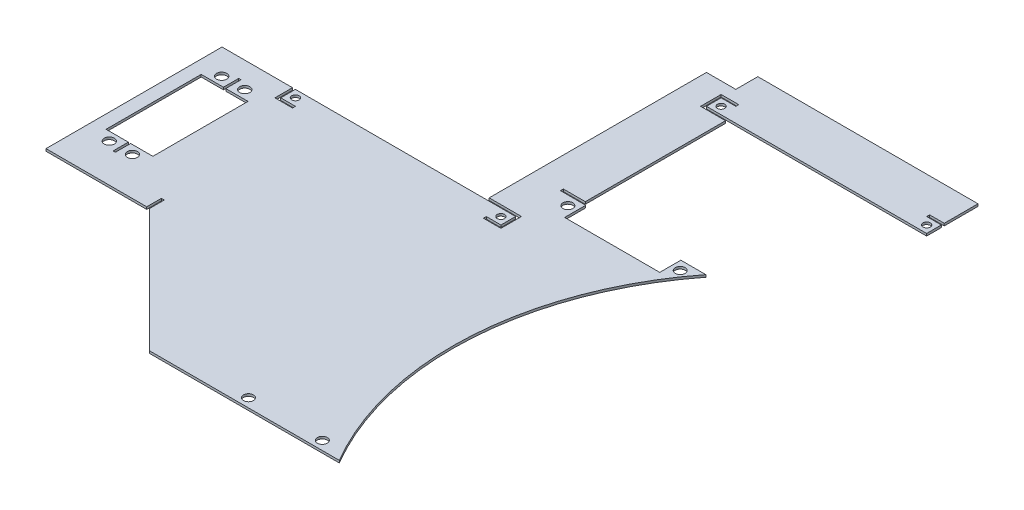
SolidWorks part; units mm, degrees
ref_plane "Front Plane" through (0, 0, 0) normal (0, 0, 1) x (1, 0, 0)
ref_plane "Top Plane" through (0, 0, 0) normal (0, 1, 0) x (1, 0, 0)
ref_plane "Right Plane" through (0, 0, 0) normal (1, 0, 0) x (0, 0, -1)
sketch "Sketch2" plane through (0, 0, 0) normal (0, 1, 0) x (1, 0, 0)
  line L1 (-127, -127) -> (127, -127)
  line L2 (-127, -127) -> (-127, 127)
  line L3 (-127, 127) -> (127, 127)
  line L4 (127, -127) -> (127, 127)
  line L5 (-127, -127) -> (127, 127) construction
  line L6 (-127, 127) -> (127, -127) construction
  point P0 (0, 0)
  dimension "D1" = 254
  dimension "D2" = 254
extrude "Boss-Extrude1" add sketch "Sketch2" along normal blind 1.0008 contours L3 L4 L1 L2
sketch "Sketch3" plane through (0, 1.0008, 0) normal (0, 1, 0) x (1, 0, 0)
  line L0 (63.5, 41.91) -> (63.5, 3.81) construction
  line L1 (127, 47.252) -> (57.15, 47.252)
  line L2 (127, 47.252) -> (127, 21.852)
  line L3 (127, 21.852) -> (57.15, 21.852)
  line L4 (57.15, 47.252) -> (57.15, 21.852)
  line L7 (64.096, 22.36) -> (70.7, 22.36) construction
  line L8 (64.096, 22.36) -> (70.7, 22.36) construction
  dimension "D1" = 6.35
  dimension "D2" = 0.508
  dimension "D3" = 25.4
extrude "Cut-Extrude1" cut sketch "Sketch3" against normal through all both and the other way through all
sketch "Sketch4" plane through (0, 1.0008, 0) normal (0, 1, 0) x (1, 0, 0)
  line L6 (127, -127) -> (127, 21.852)
  line L8 (127, 21.852) -> (57.15, 21.852)
  line L9 (127, 127) -> (-127, 127)
  line L10 (-127, 127) -> (-127, -127)
  line L11 (-127, -127) -> (127, -127)
  line L12 (127, -127) -> (127, 21.852)
  line L17 (112.9689, -127) -> (127, -127)
  line L18 (127, 21.852) -> (122.64, 21.852)
  line L19 (57.15, 21.852) -> (57.15, 47.252)
  line L22 (57.15, 47.252) -> (127, 47.252)
  line L24 (127, 47.252) -> (127, 127)
  arc A0 (127, 27.1603) -> (114.5024, -129.54) centre (227.33, -59.69) ccw construction
  arc A1 (122.64, 21.852) -> (112.9689, -127) centre (227.33, -59.69) ccw
  dimension "D1" = 0
extrude "Cut-Extrude2" cut sketch "Sketch4" against normal through all both
sketch "Sketch5" plane through (0, 1.0008, 0) normal (0, 1, 0) x (1, 0, 0)
  line L0 (63.5, -129.54) -> (63.5, -61.2891) construction
  circle A0 centre (115.577, 17.86) radius 2.1 construction
  circle A1 centre (66.977, 17.86) radius 2.1 construction
  circle A2 centre (115.577, 17.86) radius 2.1 construction
  circle A3 centre (66.977, 17.86) radius 2.1 construction
  circle A4 centre (69.85, -123.19) radius 2.15
  circle A5 centre (101.8024, -123.19) radius 2.15
  circle A6 centre (66.977, 17.86) radius 2.15
  circle A7 centre (115.577, 17.86) radius 2.15
  dimension "D1" = 6.35
  dimension "D5" = 4.3
  dimension "D2" = 12.7
  dimension "D3" = 6.35
  dimension "D4" = 6.35
extrude "Cut-Extrude3" cut sketch "Sketch5" against normal through all both
sketch "Sketch6" plane through (0, 1.0008, 0) normal (0, 1, 0) x (1, 0, 0)
  line L12 (70.7, 22.36) -> (70.7, 12.733)
  line L13 (70.7, 12.733) -> (111.854, 12.733)
  line L14 (111.854, 12.733) -> (111.854, 22.36)
  line L15 (111.854, 22.36) -> (118.458, 22.36)
  line L16 (118.458, 22.36) -> (118.458, 23.36)
  line L17 (118.458, 23.36) -> (111.854, 23.36)
  line L18 (111.854, 23.36) -> (111.854, 32.987)
  line L19 (111.854, 32.987) -> (70.7, 32.987)
  line L20 (70.7, 32.987) -> (70.7, 23.36)
  line L21 (70.7, 23.36) -> (64.096, 23.36)
  line L22 (64.096, 23.36) -> (64.096, 22.36)
  line L23 (64.096, 22.36) -> (70.7, 22.36)
  line L24 (70.7, 22.36) -> (70.7, 12.733)
  line L25 (70.7, 12.733) -> (111.854, 12.733)
  line L26 (111.854, 12.733) -> (111.854, 22.36)
  line L27 (111.854, 22.36) -> (118.458, 22.36)
  line L28 (118.458, 22.36) -> (118.458, 23.36)
  line L29 (118.458, 23.36) -> (111.854, 23.36)
  line L30 (111.854, 23.36) -> (111.854, 32.987)
  line L31 (111.854, 32.987) -> (70.7, 32.987)
  line L32 (70.7, 32.987) -> (70.7, 23.36)
  line L33 (70.7, 23.36) -> (64.096, 23.36)
  line L34 (64.096, 23.36) -> (64.096, 22.36)
  line L35 (64.096, 22.36) -> (70.7, 22.36)
  circle A1 centre (66.977, 27.86) radius 2.1
  circle A2 centre (66.977, 27.86) radius 2.1
  circle A3 centre (66.977, 17.86) radius 2.1
  circle A4 centre (66.977, 17.86) radius 2.1
  circle A5 centre (115.577, 27.86) radius 2.1
  circle A6 centre (115.577, 27.86) radius 2.1
  circle A7 centre (115.577, 17.86) radius 2.1
  circle A8 centre (115.577, 17.86) radius 2.1
  dimension "D1" = 0
  dimension "D2" = 0
  dimension "D3" = 0
  dimension "D4" = 0
  dimension "D5" = 0
extrude "Cut-Extrude4" cut sketch "Sketch6" against normal through all both
sketch "Sketch7" plane through (0, 1.0008, 0) normal (0, 1, 0) x (1, 0, 0)
  line L1 (-35.5092, 2.4892) -> (59.7408, 2.4892)
  line L2 (-35.5092, 2.4892) -> (-35.5092, 97.7392)
  line L3 (-35.5092, 97.7392) -> (59.7408, 97.7392)
  line L4 (59.7408, 2.4892) -> (59.7408, 97.7392)
  line L5 (-35.5092, 2.4892) -> (59.7408, 97.7392) construction
  line L6 (-35.5092, 97.7392) -> (59.7408, 2.4892) construction
  circle A2 centre (101.6, 22.86) radius 4.7625 construction
  circle A3 centre (101.6, 22.86) radius 4.699 construction
  point P0 (12.1158, 50.1142)
  dimension "D1" = 95.25
  dimension "D3" = 20.3708
  dimension "D2" = 137.1092
extrude "Cut-Extrude5" cut sketch "Sketch7" against normal through all both
sketch "Sketch8" plane through (0, 1.0008, 0) normal (0, 1, 0) x (1, 0, 0)
  line L0 (127, 47.252) -> (127, 127)
  line L2 (127, 127) -> (-127, 127)
  line L3 (-127, 127) -> (-127, -127)
  line L4 (-127, -127) -> (-35.5092, -127)
  line L5 (-127, -127) -> (112.9689, -127) construction
  line L6 (-35.5092, -127) -> (-35.5092, 47.252)
  line L7 (-35.5092, 47.252) -> (127, 47.252)
  line L9 (-35.5092, 97.7392) -> (-35.5092, 2.4892) construction
  point P2 (0, 0)
extrude "Cut-Extrude6" cut sketch "Sketch8" against normal through all both
sketch "Sketch17" plane through (0, 1.0008, 0) normal (0, 1, 0) x (1, 0, 0)
  line L1 (59.7408, 2.4892) -> (47.0408, 2.4892)
  line L2 (59.7408, 2.4892) -> (59.7408, 85.0392)
  line L3 (59.7408, 97.7392) -> (47.0408, 97.7392)
  line L4 (47.0408, 2.4892) -> (47.0408, 97.7392)
  line L5 (-35.5092, 2.4892) -> (59.7408, 2.4892) construction
  line L6 (59.7408, 97.7392) -> (154.9908, 97.7392)
  line L8 (59.7408, 85.0392) -> (154.9908, 85.0392)
  line L9 (154.9908, 97.7392) -> (154.9908, 85.0392)
  dimension "D1" = 12.7
extrude "Boss-Extrude4" add sketch "Sketch17" against normal up to surface (1.0008 mm away) up to face at (62.6286, 0, 13.466)
sketch "Sketch18" plane through (0, 1.0008, 0) normal (0, 1, 0) x (1, 0, 0)
  line L0 (47.0408, 2.4892) -> (59.7408, 2.4892)
  point P3 (0, 0)
extrude "Cut-Extrude-Thin4" cut sketch "Sketch18" against normal through all both and the other way through all thin thin type one direction reverse wall 1.27
sketch "Sketch9" plane through (0, 1.0008, 0) normal (0, 1, 0) x (1, 0, 0)
  line L0 (-35.5092, -60.5651) -> (30.9257, -127)
  line L1 (-35.5092, -127) -> (-35.5092, 2.4892) construction
  line L2 (-35.5092, -127) -> (112.9689, -127) construction
  line L3 (-35.5092, -127) -> (30.9257, -127)
  line L4 (-35.5092, -127) -> (-35.5092, -60.5651)
  circle A0 centre (101.727, 22.86) radius 149.6811 construction
  circle A1 centre (101.727, 22.86) radius 156.0311 construction
  dimension "D1" = 6.35
  dimension "D2" = 45
extrude "Cut-Extrude7" cut sketch "Sketch9" against normal through all both
sketch "Sketch10" plane through (0, 1.0008, 0) normal (0, 1, 0) x (1, 0, 0)
  line L37 (59.7408, 21.852) -> (59.7408, 85.0392) construction
  line L38 (59.7408, 83.7692) -> (69.2658, 83.7692)
  line L39 (59.7408, 83.7692) -> (59.7408, 23.122)
  line L40 (59.7408, 23.122) -> (69.2658, 23.122)
  line L41 (69.2658, 83.7692) -> (69.2658, 23.122)
  line L42 (70.7, 21.852) -> (59.7408, 21.852) construction
  line L43 (59.7408, 85.0392) -> (154.9908, 85.0392) construction
  line L44 (154.9908, 97.7392) -> (47.0408, 97.7392) construction
  line L45 (59.7408, 97.7392) -> (154.9908, 97.7392)
  line L46 (59.7408, 97.7392) -> (59.7408, 107.2642)
  line L47 (59.7408, 107.2642) -> (154.9908, 107.2642)
  line L48 (154.9908, 97.7392) -> (154.9908, 107.2642)
  point P18 (0, 0)
  point P19 (69.2658, 83.7692)
  point P20 (76.2868, 107.2642)
  line M23 (-35.5092, -60.5651) -> (30.9257, -127)
  line M24 (30.9257, -127) -> (112.9689, -127)
  line M33 (-35.5092, 2.4892) -> (-35.5092, -60.5651)
  dimension "D1" = 1.27
  dimension "D2" = 1.27
  dimension "D3" = 9.525
extrude "Boss-Extrude2" add sketch "Sketch10" against normal up to surface (1.0008 mm away) contours M23 | M24 | M33 | L46 L45 L48 L47 | L39 L38 L41 L40 up to face at (69.4562, 0, -10.4618)
sketch "Sketch14" plane through (0, 1.0008, 0) normal (0, 1, 0) x (1, 0, 0)
  line L0 (-61.5112, -12.271) -> (-41.2572, -53.425) construction
  line L5 (-61.5112, -12.271) -> (-51.8842, -12.271)
  line L6 (-61.5112, -12.271) -> (-61.5112, -53.425)
  line L7 (-61.5112, -53.425) -> (-51.8842, -53.425)
  line L12 (-41.2572, -12.271) -> (-41.2572, -53.425)
  line L17 (-35.5092, -5.1308) -> (-67.2592, -5.1308)
  line L22 (-35.5092, -60.5651) -> (-35.5092, 2.4892) construction
  line L23 (-67.2592, -5.1308) -> (-67.2592, -60.5651)
  line L24 (-67.2592, -60.5651) -> (-35.5092, -60.5651)
  line L25 (-35.5092, -60.5651) -> (-35.5092, -5.1308)
  line L34 (-41.2572, -12.271) -> (-61.5112, -53.425) construction
  line L35 (-56.3842, -8.548) -> (-46.3842, -57.148) construction
  line L36 (-56.3842, -57.148) -> (-46.3842, -8.548) construction
  line L37 (-50.8842, -53.425) -> (-41.2572, -53.425)
  line L38 (-51.8842, -53.425) -> (-51.8842, -60.029)
  line L39 (-51.8842, -60.029) -> (-50.8842, -60.029)
  line L40 (-50.8842, -53.425) -> (-50.8842, -60.029)
  line L41 (-51.3842, -32.848) -> (-15.6253, -32.848) construction
  line L42 (-51.8842, -5.667) -> (-50.8842, -5.667)
  line L43 (-51.8842, -12.271) -> (-51.8842, -5.667)
  line L44 (-50.8842, -12.271) -> (-50.8842, -5.667)
  line L45 (-50.8842, -12.271) -> (-41.2572, -12.271)
  line L47 (-67.2592, -5.1308) -> (-67.2592, 2.4892)
  line L48 (-67.2592, 2.4892) -> (-35.5092, 2.4892)
  line L49 (-35.5092, 2.4892) -> (-35.5092, -5.1308)
  line L51 (-35.5092, 2.4892) -> (59.7408, 2.4892) construction
  line L52 (-67.2592, -60.5651) -> (-67.2592, -73.66)
  line L53 (-67.2592, -73.66) -> (-22.4143, -73.66)
  line L54 (30.9257, -127) -> (-35.5092, -60.5651) construction
  line L57 (-22.4143, -73.66) -> (-35.5092, -60.5651)
  circle A8 centre (-56.3842, -57.148) radius 2.2
  circle A9 centre (-46.3842, -57.148) radius 2.2
  circle A10 centre (-56.3842, -8.548) radius 2.2
  circle A11 centre (-46.3842, -8.548) radius 2.2
  point P9 (-51.3842, -60.029)
  point P19 (-51.3842, -32.848)
  point P20 (-51.3842, -32.848)
  point P37 (-67.2592, -32.848)
  point P39 (-51.3842, -60.5651)
  point P42 (0, 0)
  dimension "D3" = 48.6
  dimension "D4" = 4.4
  dimension "D2" = 10
  dimension "D5" = 41.154
  dimension "D6" = 20.254
  dimension "D7" = 1
  dimension "D8" = 6.604
  dimension "D9" = 31.75
  dimension "D10" = 7.62
  dimension "D11" = 53.34
extrude "Boss-Extrude3" add sketch "Sketch14" against normal up to surface (1.0008 mm away) contours L49 L48 L47 L17 | L24 L25 L17 L23 A11 A10 A9 A8 L44 L45 L12 L37 L40 L39 L38 L7 L6 L5 L43 L42 | L24 region at (-36.148, 1.0008, 32.848) region at (-51.3842, 1.0008, 1.3208) region at (-47.9239, 1.0008, 67.4857) up to face at (67.75, 0, -26.3548)
sketch "Sketch15" plane through (0, 1.0008, 0) normal (0, 1, 0) x (1, 0, 0)
  line L0 (-22.4143, -73.66) -> (-22.4143, -67.31)
  dimension "D1" = 6.35
extrude "Cut-Extrude-Thin3" cut sketch "Sketch15" against normal through all both and the other way through all thin thin type one direction reverse wall 1.27
sketch "Sketch19" plane through (0, 1.0008, 0) normal (0, 1, 0) x (1, 0, 0)
  line L0 (154.9908, 85.0392) -> (154.9908, 107.2642) construction
  line L1 (59.7408, 85.0392) -> (154.9908, 85.0392) construction
  line L2 (59.7408, 83.7692) -> (59.7408, 85.0392) construction
  line L3 (-67.2592, 2.4892) -> (59.7408, 2.4892) construction
  line L4 (59.7408, 2.4892) -> (59.7408, 3.7592) construction
  line L5 (62.9158, 88.2142) -> (151.8158, 88.2142) construction
  line L6 (-32.3342, -0.6858) -> (56.5658, -0.6858) construction
  circle A0 centre (56.5658, -0.6858) radius 1.5875
  circle A1 centre (-32.3342, -0.6858) radius 1.5875
  circle A2 centre (151.8158, 88.2142) radius 1.5875
  circle A3 centre (62.9158, 88.2142) radius 1.5875
  point P12 (0, 0)
  dimension "D3" = 3.175
  dimension "D1" = 3.175
  dimension "D2" = 3.175
  dimension "D4" = 3.175
  dimension "D5" = 3.175
  dimension "D6" = 3.175
extrude "Cut-Extrude8" cut sketch "Sketch19" against normal through all both and the other way through all
sketch "Sketch20" plane through (0, 1.0008, 0) normal (0, 1, 0) x (1, 0, 0)
  line L0 (-35.5092, 2.4892) -> (-35.5092, -3.8608)
  line L1 (-67.2592, 2.4892) -> (59.7408, 2.4892) construction
  line L2 (-35.5092, -3.8608) -> (-29.1592, -3.8608)
  line L3 (59.7408, 2.4892) -> (59.7408, -3.8608)
  line L4 (59.7408, -3.8608) -> (53.3908, -3.8608)
  line L5 (59.7408, 85.0392) -> (59.7408, 91.3892)
  line L6 (59.7408, 91.3892) -> (66.0908, 91.3892)
  line L7 (154.9908, 91.3892) -> (154.9908, 85.0392) construction
  line L8 (148.6408, 91.3892) -> (154.9908, 91.3892)
  line L9 (154.9908, 85.0392) -> (154.9908, 107.2642) construction
  line L10 (58.4708, 85.0392) -> (58.4708, 92.6592)
  line L11 (58.4708, 92.6592) -> (66.0908, 92.6592)
  line L12 (148.6408, 92.6592) -> (154.9908, 92.6592)
  line L13 (61.0108, 2.4892) -> (61.0108, -5.1308)
  line L14 (61.0108, -5.1308) -> (53.3908, -5.1308)
  line L15 (-36.7792, 2.4892) -> (-36.7792, -5.1308)
  line L16 (-36.7792, -5.1308) -> (-29.1592, -5.1308)
  line L17 (-36.7792, 2.4892) -> (-35.5092, 2.4892)
  line L18 (-29.1592, -3.8608) -> (-29.1592, -5.1308)
  line L19 (148.6408, 92.6592) -> (148.6408, 91.3892)
  line L20 (154.9908, 91.3892) -> (154.9908, 92.6592)
  line L21 (59.7408, 85.0392) -> (58.4708, 85.0392)
  line L22 (66.0908, 91.3892) -> (66.0908, 92.6592)
  line L23 (59.7408, 2.4892) -> (61.0108, 2.4892)
  line L24 (53.3908, -3.8608) -> (53.3908, -5.1308)
  line L25 (59.7408, 85.0392) -> (59.7408, 83.7692)
  line L26 (59.7408, 83.7692) -> (69.2658, 83.7692) construction
  line L27 (59.7408, 83.7692) -> (58.4708, 83.7692)
  line L28 (58.4708, 83.7692) -> (58.4708, 85.0392)
  line L29 (59.7408, 2.4892) -> (59.7408, 3.7592)
  line L30 (59.7408, 3.7592) -> (61.0108, 3.7592)
  line L31 (61.0108, 3.7592) -> (61.0108, 2.4892)
  dimension "D1" = 6.35
  dimension "D2" = 95.25
  dimension "D3" = 1.27
  dimension "D4" = 1.27
extrude "Cut-Extrude12" cut sketch "Sketch20" against normal through all both contours L28 L27 L25 L21 | L6 L22 L11 L10 L21 L5 | L31 L30 L29 L23 | L4 L24 L14 L13 L23 L3 | L18 L2 L0 L17 L15 L16 | L8 L20 L12 L19 region at (-35.617, 1.0008, 0.6858) region at (60.3758, 1.0008, -2.3814) region at (60.3758, 1.0008, -3.1242) region at (59.1058, 1.0008, -85.147) region at (59.1058, 1.0008, -84.4042)
equation "\"looseTol\"= 0.02in"
equation "\"tightTol\"= 0.005in"
equation "\"normTol\"= 0.01in"
equation "\"D2@Sketch3\"=\"looseTol\""
equation "\"D5@Sketch5\"=4.3mm"
